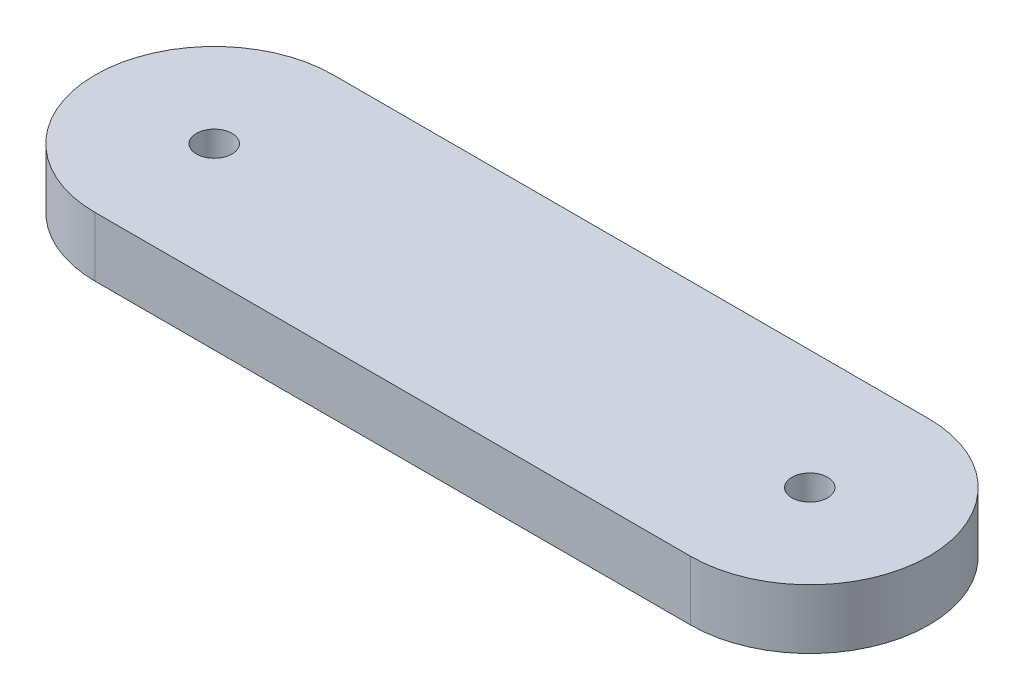
SolidWorks part; units mm, degrees
ref_plane "Front Plane" through (0, 0, 0) normal (0, 0, 1) x (1, 0, 0)
ref_plane "Top Plane" through (0, 0, 0) normal (0, 1, 0) x (1, 0, 0)
ref_plane "Right Plane" through (0, 0, 0) normal (1, 0, 0) x (0, 0, -1)
sketch "Sketch1" plane through (0, 0, 0) normal (0, 1, 0) x (1, 0, 0)
  line L0 (-25, 0) -> (25, 0) construction
  line L1 (-25, 10) -> (25, 10)
  line L2 (-25, -10) -> (25, -10)
  arc A0 (-25, 10) -> (-25, -10) centre (-25, 0) ccw
  arc A1 (25, -10) -> (25, 10) centre (25, 0) ccw
  point P3 (0, 0)
  dimension "D1" = 10
  dimension "D2" = 50
extrude "Boss-Extrude1" add sketch "Sketch1" along normal blind 5
sketch "Sketch2" plane through (0, 5, 0) normal (0, 1, 0) x (1, 0, 0)
  line L0 (0, -2.75) -> (0, 2.75) construction
  circle A0 centre (-25, 0) radius 1.5
  circle A1 centre (25, 0) radius 1.5
  dimension "D1" = 3
extrude "Cut-Extrude1" cut sketch "Sketch2" against normal up to next
equation "\"Length\"= 50mm"
equation "\"Radius\"= 10mm"
equation "\"D1@Sketch1\"= \"Radius\""
equation "\"D2@Sketch1\" = \"Length\""
equation "\"Thick\"= 5mm"
equation "\"D1@Boss-Extrude1\"= \"Thick\""
